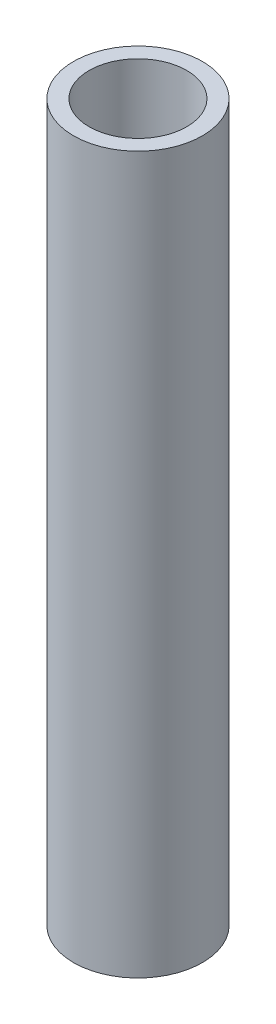
SolidWorks part; units mm, degrees
material "PVC 0.007 Plasticized"
ref_plane "Front Plane" through (0, 0, 0) normal (0, 0, 1) x (1, 0, 0)
ref_plane "Top Plane" through (0, 0, 0) normal (0, 1, 0) x (1, 0, 0)
ref_plane "Right Plane" through (0, 0, 0) normal (1, 0, 0) x (0, 0, -1)
sketch "Sketch1" plane through (0, 0, 0) normal (0, 1, 0) x (1, 0, 0)
  circle A0 centre (0, 0) radius 12.573
  circle A1 centre (0, 0) radius 9.525
  dimension "D1" = 19.05
  dimension "D2" = 25.146
extrude "Boss-Extrude1" add sketch "Sketch1" along normal blind 139.7
